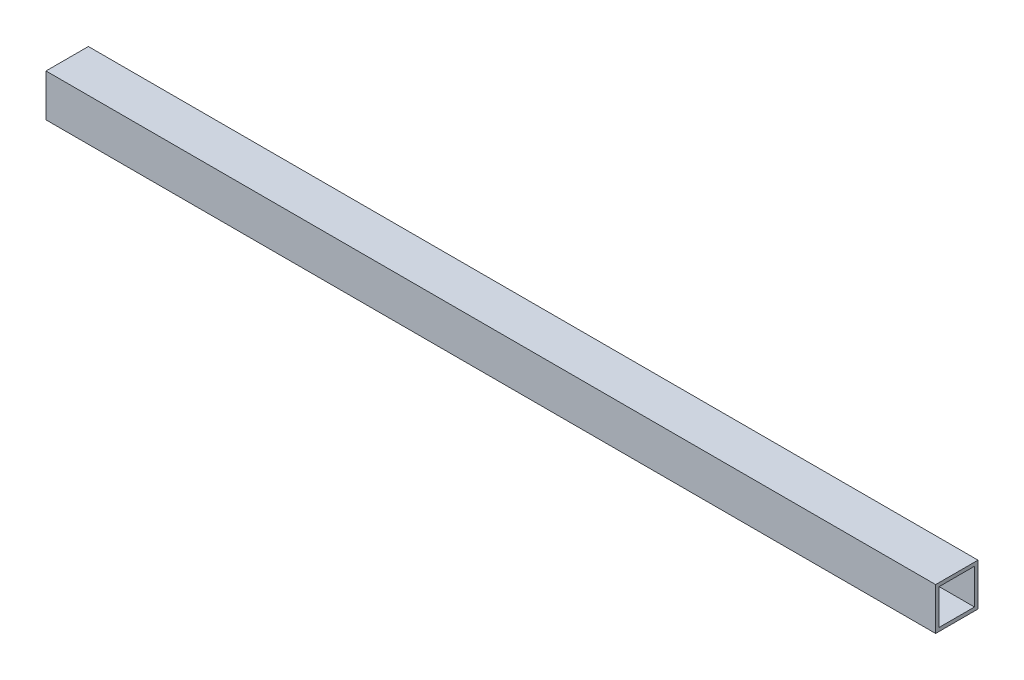
SolidWorks part; units mm, degrees
material "6063-T6"
ref_plane "Front Plane" through (0, 0, 0) normal (0, 0, 1) x (1, 0, 0)
ref_plane "Top Plane" through (0, 0, 0) normal (0, 1, 0) x (1, 0, 0)
ref_plane "Right Plane" through (0, 0, 0) normal (1, 0, 0) x (0, 0, -1)
sketch "Sketch1" plane through (0, 0, 0) normal (1, 0, 0) x (0, 0, -1)
  line L0 (3.175, 3.175) -> (3.175, 34.925)
  line L1 (0, 0) -> (38.1, 0)
  line L2 (0, 0) -> (0, 38.1)
  line L3 (0, 38.1) -> (38.1, 38.1)
  line L4 (38.1, 0) -> (38.1, 38.1)
  line L5 (3.175, 34.925) -> (34.925, 34.925)
  line L6 (34.925, 3.175) -> (34.925, 34.925)
  line L7 (3.175, 3.175) -> (34.925, 3.175)
  dimension "D1" = 38.1
  dimension "D2" = 3.175
extrude "Boss-Extrude1" add sketch "Sketch1" along normal blind 800.1
